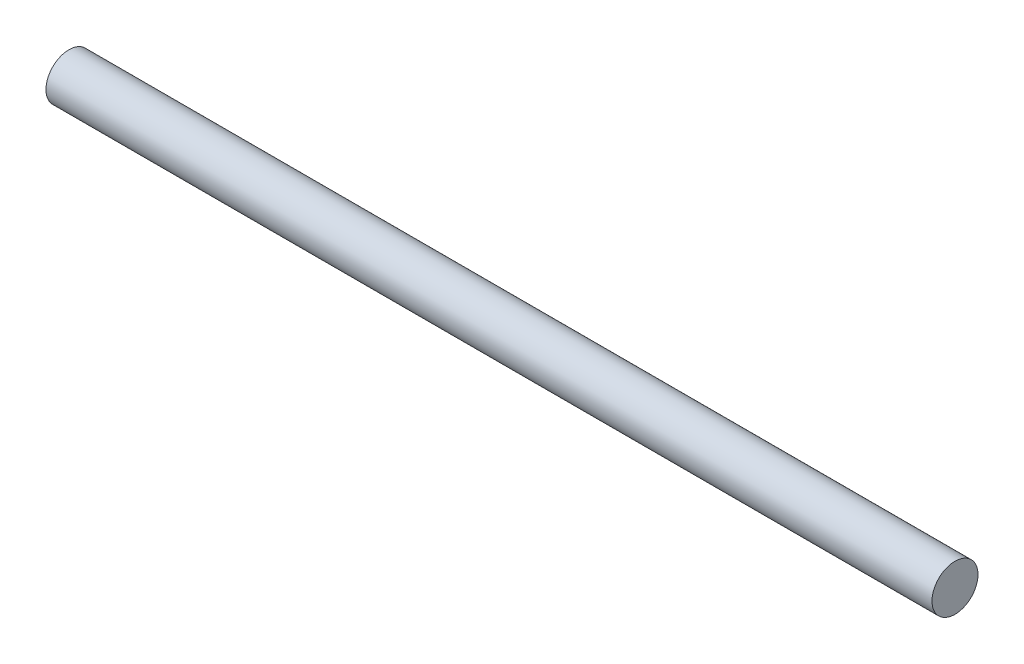
SolidWorks part; units mm, degrees
ref_plane "Plano frontal" through (0, 0, 0) normal (0, 0, 1) x (1, 0, 0)
ref_plane "Plano superior" through (0, 0, 0) normal (0, 1, 0) x (1, 0, 0)
ref_plane "Plano direito" through (0, 0, 0) normal (1, 0, 0) x (0, 0, -1)
sketch "Esboço1" plane through (0, 0, 0) normal (1, 0, 0) x (0, 0, -1)
  circle A0 centre (0, 0) radius 4
base flange "Flange-base1" sketch "Esboço1" thickness 154 reverse thickness direction no parameters "D1"=10
sketch "Curva-Linhas1" [suppressed] plane through (0, 0, 0) normal (0, 1, 0) x (1, 0, 0)
sketch "Caixa delimitadora1" [suppressed] plane through (0, 0, 0) normal (0, 1, 0) x (1, 0, 0)
sheet metal parameters "Chapa metálica1" thickness 154 parameters "D1"=10
flat pattern "Padrão-Plano1" [suppressed]
sketch "Curva-Linhas2" plane through (0, 0, 0) normal (0, 1, 0) x (1, 0, 0)
sketch3d "Caixa delimitadora2" [suppressed]
  line L0 (-3.9323, -4.0664, 0) -> (4.0663, -3.9324, 0) construction
  line L1 (-4.0663, 3.9322, 0) -> (3.9323, 4.0661, 0) construction
  line L2 (-3.9323, -4.0664, 0) -> (-4.0663, 3.9322, 0) construction
  line L3 (4.0663, -3.9324, 0) -> (3.9323, 4.0661, 0) construction
